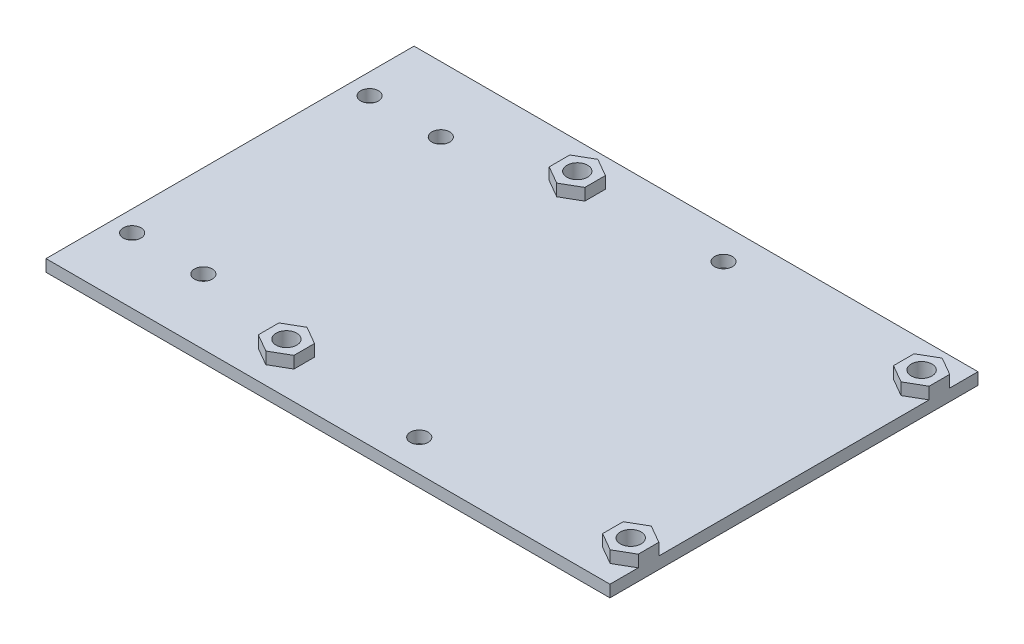
SolidWorks part; units mm, degrees
ref_plane "Front Plane" through (0, 0, 0) normal (0, 0, 1) x (1, 0, 0)
ref_plane "Top Plane" through (0, 0, 0) normal (0, 1, 0) x (1, 0, 0)
ref_plane "Right Plane" through (0, 0, 0) normal (1, 0, 0) x (0, 0, -1)
sketch "Croquis1" plane through (0, 0, 0) normal (0, 1, 0) x (1, 0, 0)
  line L1 (-47.5, 31) -> (47.5, 31)
  line L2 (-47.5, 31) -> (-47.5, -31)
  line L3 (-47.5, -31) -> (47.5, -31)
  line L4 (47.5, 31) -> (47.5, -31)
  line L5 (-47.5, 31) -> (47.5, -31) construction
  line L6 (-47.5, -31) -> (47.5, 31) construction
  line L7 (47.5, 22.7679) -> (47.5, 26.2321)
  line L8 (47.5, 26.2321) -> (44.5, 27.9641)
  line L9 (44.5, 27.9641) -> (41.5, 26.2321)
  line L10 (41.5, 26.2321) -> (41.5, 22.7679)
  line L11 (41.5, 22.7679) -> (44.5, 21.0359)
  line L12 (44.5, 21.0359) -> (47.5, 22.7679)
  line L13 (47.5, -26.2321) -> (47.5, -22.7679)
  line L14 (47.5, -22.7679) -> (44.5, -21.0359)
  line L15 (44.5, -21.0359) -> (41.5, -22.7679)
  line L16 (41.5, -22.7679) -> (41.5, -26.2321)
  line L17 (41.5, -26.2321) -> (44.5, -27.9641)
  line L18 (44.5, -27.9641) -> (47.5, -26.2321)
  line L19 (-10.5, 22.7679) -> (-10.5, 26.2321)
  line L20 (-10.5, 26.2321) -> (-13.5, 27.9641)
  line L21 (-13.5, 27.9641) -> (-16.5, 26.2321)
  line L22 (-16.5, 26.2321) -> (-16.5, 22.7679)
  line L23 (-16.5, 22.7679) -> (-13.5, 21.0359)
  line L24 (-13.5, 21.0359) -> (-10.5, 22.7679)
  line L25 (-10.5, -26.2321) -> (-10.5, -22.7679)
  line L26 (-10.5, -22.7679) -> (-13.5, -21.0359)
  line L27 (-13.5, -21.0359) -> (-16.5, -22.7679)
  line L28 (-16.5, -22.7679) -> (-16.5, -26.2321)
  line L29 (-16.5, -26.2321) -> (-13.5, -27.9641)
  line L30 (-13.5, -27.9641) -> (-10.5, -26.2321)
  circle A0 centre (44.5, -24.5) radius 1.75
  circle A1 centre (44.5, 24.5) radius 1.75
  circle A2 centre (10, 25.63) radius 1.5
  circle A3 centre (10, -25.63) radius 1.5
  circle A4 centre (44.5, 24.5) radius 3 construction
  circle A5 centre (44.5, -24.5) radius 3 construction
  circle A6 centre (-43.99, 20) radius 1.5
  circle A7 centre (-31.99, 20) radius 1.5
  circle A8 centre (-43.99, -20) radius 1.5
  circle A9 centre (-31.99, -20) radius 1.5
  circle A10 centre (-13.5, 24.5) radius 1.75
  circle A11 centre (-13.5, -24.5) radius 1.75
  circle A12 centre (-13.5, 24.5) radius 3 construction
  circle A13 centre (-13.5, -24.5) radius 3 construction
  point P0 (0, 0)
  dimension "D6" = 3
  dimension "D9" = 3.5
  dimension "D14" = 3
  dimension "D1" = 62
  dimension "D2" = 95
  dimension "D3" = 49
  dimension "D4" = 51.26
  dimension "D5" = 25.63
  dimension "D7" = 24.5
  dimension "D8" = 3
  dimension "D10" = 10
  dimension "D11" = 40
  dimension "D12" = 20
  dimension "D13" = 12
  dimension "D15" = 15.51
  dimension "D16" = 58
extrude "Saliente-Extruir1" add sketch "Croquis1" along normal blind 2 contours A2 | A3 | A1 | A0 | A6 | A7 | A8 | A9 | A10 | A11 | L3 L4 L1 L2 region at (44.5, 0, 24.5) region at (44.5, 0, -24.5) region at (10, 0, -25.63) region at (10, 0, 25.63) region at (-43.99, 0, -20) region at (-31.99, 0, -20) region at (-43.99, 0, 20) region at (-31.99, 0, 20) region at (-13.5, 0, -24.5) region at (-13.5, 0, 24.5)
extrude "Saliente-Extruir2" add sketch "Croquis1<4>" along normal blind 4 contours L23 L24 L19 L20 L21 L22 A10 | L29 L30 L25 L26 L27 L28 A11 | L17 L18 L4 L14 L15 L16 A0 | L11 L12 L4 L8 L9 L10 A1 region at (47.4083, 0, -24.5) region at (45.9542, 0, 27.0187) region at (-12.0458, 0, -21.9813) region at (-12.0458, 0, 27.0187)
sketch "Croquis1<4>" plane through (0, 0, 0) normal (0, 1, 0) x (1, 0, 0) same geometry as "Croquis1"
equation "\"D5@Croquis1\"=\"D4@Croquis1\"/2"
equation "\"D7@Croquis1\"=\"D3@Croquis1\"/2"
equation "\"D12@Croquis1\"=\"D11@Croquis1\"/2"
